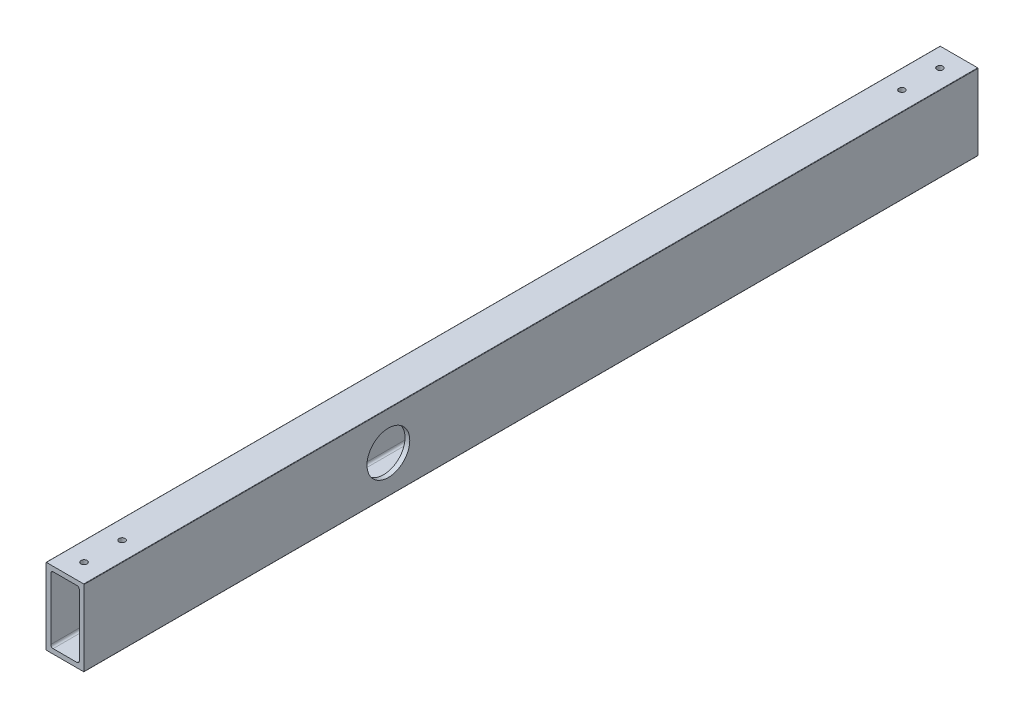
SolidWorks part; units mm, degrees
material "3.0205 (EN-AW 1200)"
ref_plane "Front Plane" through (0, 0, 0) normal (0, 0, 1) x (1, 0, 0)
ref_plane "Top Plane" through (0, 0, 0) normal (0, 1, 0) x (1, 0, 0)
ref_plane "Right Plane" through (0, 0, 0) normal (1, 0, 0) x (0, 0, -1)
ref_plane "Plane1" through (0, 0, 0) normal (0, 0, -1) x (-1, 0, 0)
sketch "Sketch1" plane through (0, 0, 0) normal (0, 0, -1) x (-1, 0, 0)
  line L0 (-3.175, 46.0375) -> (-3.175, 4.7625)
  line L1 (-4.7625, 3.175) -> (-20.6375, 3.175)
  line L2 (-22.225, 4.7625) -> (-22.225, 46.0375)
  line L3 (-20.6375, 47.625) -> (-4.7625, 47.625)
  line L4 (0, 0.254) -> (0, 50.546)
  line L5 (-0.254, 50.8) -> (-25.146, 50.8)
  line L6 (-25.4, 50.546) -> (-25.4, 0.254)
  line L7 (-25.146, 0) -> (-0.254, 0)
  arc A0 (-3.175, 4.7625) -> (-4.7625, 3.175) centre (-4.7625, 4.7625) cw
  arc A1 (-20.6375, 3.175) -> (-22.225, 4.7625) centre (-20.6375, 4.7625) cw
  arc A2 (-22.225, 46.0375) -> (-20.6375, 47.625) centre (-20.6375, 46.0375) cw
  arc A3 (-4.7625, 47.625) -> (-3.175, 46.0375) centre (-4.7625, 46.0375) cw
  arc A4 (-0.254, 0) -> (0, 0.254) centre (-0.254, 0.254) ccw
  arc A5 (0, 50.546) -> (-0.254, 50.8) centre (-0.254, 50.546) ccw
  arc A6 (-25.146, 50.8) -> (-25.4, 50.546) centre (-25.146, 50.546) ccw
  arc A7 (-25.4, 0.254) -> (-25.146, 0) centre (-25.146, 0.254) ccw
extrude "Boss-Extrude1" add sketch "Sketch1" against normal blind 596.9
sketch "Sketch2" plane through (0, 50.8, 0) normal (0, 1, 0) x (1, 0, 0)
  line L0 (0.254, -596.9) -> (25.146, -596.9) construction
  line L1 (25.146, -298.45) -> (0, -298.45) construction
  line L2 (25.146, -596.9) -> (25.146, 0) construction
  line L3 (0, -596.9) -> (0, 0) construction
  circle A0 centre (12.7, -584.2) radius 2.032
  circle A1 centre (12.7, -558.8) radius 2.032
  circle A2 centre (12.7, -38.1) radius 2.032
  circle A3 centre (12.7, -12.7) radius 2.032
  dimension "D1" = 4.064
  dimension "D2" = 4.064
  dimension "D3" = 12.7
  dimension "D4" = 25.4
extrude "Cut-Extrude1" cut sketch "Sketch2" against normal through all
ref_plane "Plane2" through (224.155, 46.0375, 596.9) normal (0, 0, -1) x (-1, 0, 0)
sketch "Sketch5" plane through (25.4, 0, 0) normal (1, 0, 0) x (0, 0, -1)
  line L0 (-596.9, 50.546) -> (0, 50.546) construction
  line L1 (-596.9, -118.11) -> (-596.9, 210.185) construction
  circle A0 centre (-393.7, 25.146) radius 14.2875
  dimension "D1" = 28.575
  dimension "D2" = 25.4
  dimension "D3" = 203.2
extrude "Cut-Extrude2" cut sketch "Sketch5" against normal through all
